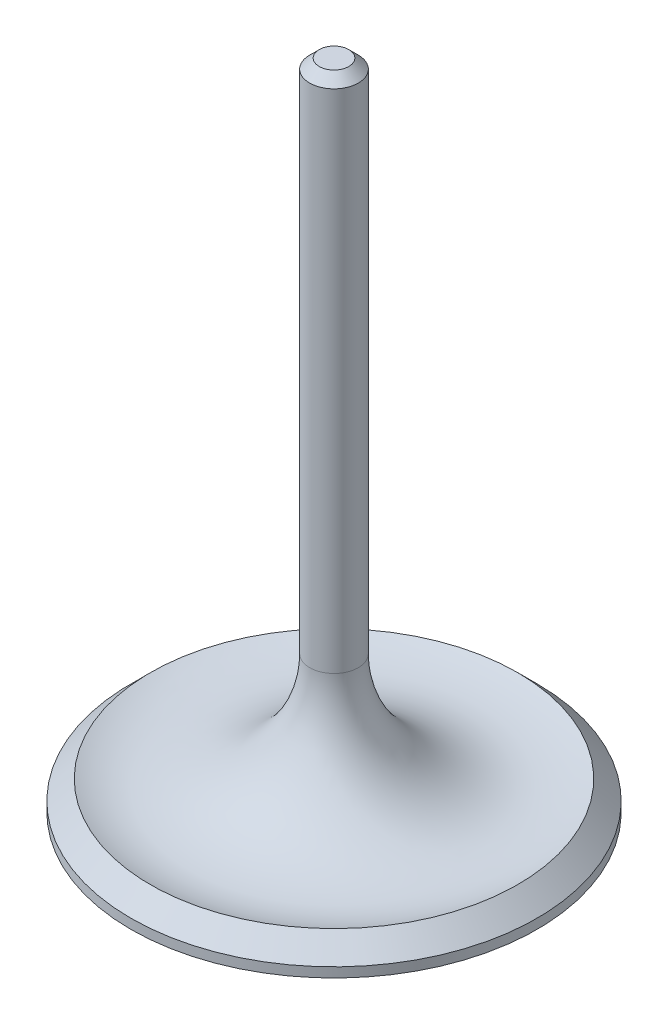
SolidWorks part; units mm, degrees
ref_plane "Front Plane" through (0, 0, 0) normal (0, 0, 1) x (1, 0, 0)
ref_plane "Top Plane" through (0, 0, 0) normal (0, 1, 0) x (1, 0, 0)
ref_plane "Right Plane" through (0, 0, 0) normal (1, 0, 0) x (0, 0, -1)
sketch "Sketch1" plane through (0, 0, 0) normal (0, 0, 1) x (1, 0, 0)
  line L0 (0, -342.0306) -> (0, 16759.4974) construction
  line L1 (-342.0306, 0) -> (16759.4974, 0) construction
  line L2 (0, 0) -> (26.6, 0)
  line L3 (26.6, 0) -> (26.6, 1.27)
  line L4 (3.18, 17.9827) -> (3.18, 85.55)
  line L5 (26.6, 1.27) -> (24.06, 3.81)
  line L6 (0, 0) -> (0, 85.55)
  line L7 (0, 85.55) -> (3.18, 85.55)
  arc A0 (24.06, 3.81) -> (3.18, 17.9827) centre (18.43, 17.9827) cw
  dimension "D5" = 15.25
  dimension "D6" = 85.55
  dimension "D1" = 26.6
  dimension "D2" = 1.27
  dimension "D3" = 45
  dimension "D4" = 3.81
  dimension "D7" = 3.18
revolve "Revolve1" add sketch "Sketch1" angle 360 about L6
chamfer "Chamfer1" distance 1.25 angle 45 1 edges at (0, 85.55, -3.18)
ref_axis "Axis1" through (0, 84.3, 0) along (0, -1, 0)
